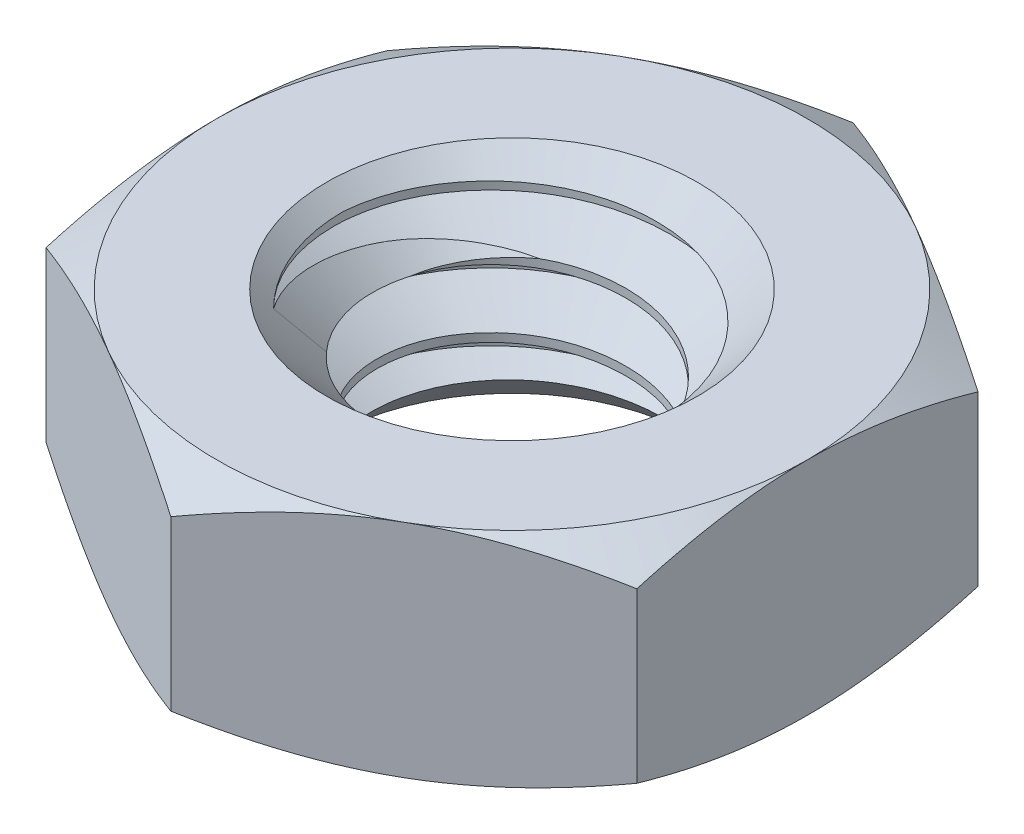
SolidWorks part; units mm, degrees
ref_plane "Front Plane" through (0, 0, 0) normal (0, 0, 1) x (1, 0, 0)
ref_plane "Top Plane" through (0, 0, 0) normal (0, 1, 0) x (1, 0, 0)
ref_plane "Right Plane" through (0, 0, 0) normal (1, 0, 0) x (0, 0, -1)
sketch "Sketch1" plane through (0, 0, 0) normal (0, 0, 1) x (1, 0, 0)
  line L0 (0, -2.0828) -> (0, 2.0828) construction
  line L1 (3.175, 2.0828) -> (-3.175, 2.0828) construction
  line L2 (-5.5626, -2.0828) -> (5.5626, -2.0828) construction
  line L3 (3.175, 2.0828) -> (3.175, 0.8128) construction
  point P4 (0, 0)
  point P8 (0, 2.0828)
  point P10 (0, -2.0828)
  dimension "Height" = 4.1656
  dimension "Width" = 11.1252
  dimension "Thread Dia" = 6.35
  dimension "Pitch" = 1.27
sketch "Sketch2" plane through (0, 0, 0) normal (0, 1, 0) x (1, 0, 0)
  line L1 (0, 6.4231) -> (-5.5626, 3.2116)
  line L2 (-5.5626, 3.2116) -> (-5.5626, -3.2116)
  line L3 (-5.5626, -3.2116) -> (0, -6.4231)
  line L4 (0, -6.4231) -> (5.5626, -3.2116)
  line L5 (5.5626, -3.2116) -> (5.5626, 3.2116)
  line L6 (5.5626, 3.2116) -> (0, 6.4231)
  circle A0 centre (0, 0) radius 5.5626 construction
  circle A1 centre (0, 0) radius 3.175
  point P11 (0, -3.175)
  point P14 (0, 0)
extrude "Boss-Extrude1" add sketch "Sketch2" along normal up to vertex (2.0828 mm away) and the other way up to vertex (2.0828 mm away) up to point (0, 2.0828, 0) other way up to point (0, -2.0828, 0)
sketch "Sketch3" plane through (0, 0, 0) normal (1, 0, 0) x (0, 0, -1)
  line L0 (-6.4231, 1.586) -> (-5.5626, 2.0828)
  line L1 (-6.4231, 2.0828) -> (-6.4231, -2.0828) construction
  line L2 (-6.4231, 2.0828) -> (-3.2116, 2.0828) construction
  line L3 (-6.4231, -1.586) -> (-5.5626, -2.0828)
  line L4 (-6.4231, -2.0828) -> (-3.2116, -2.0828) construction
  line L5 (-6.4231, 1.586) -> (-6.4231, 2.0828)
  line L6 (-6.4231, 2.0828) -> (-5.5626, 2.0828)
  line L7 (-6.4231, -1.586) -> (-6.4231, -2.0828)
  line L8 (-6.4231, -2.0828) -> (-5.5626, -2.0828)
  line L9 (-5.5626, 2.0828) -> (-5.5626, -2.0828) construction
  line L10 (-3.4925, 2.0828) -> (-3.175, 2.0828)
  line L11 (-3.2116, 2.0828) -> (3.2116, 2.0828) construction
  line L12 (-3.175, 2.0828) -> (-3.175, 1.7653)
  line L13 (-3.175, 1.7653) -> (-3.4925, 2.0828)
  line L14 (-3.4925, -2.0828) -> (-3.175, -2.0828)
  line L15 (-3.2116, -2.0828) -> (3.2116, -2.0828) construction
  line L16 (-3.175, -2.0828) -> (-3.175, -1.7653)
  line L17 (-3.4925, -2.0828) -> (-3.175, -1.7653)
  line L18 (-3.175, 1.7653) -> (-3.175, -1.7653) construction
  line L19 (3.175, 0) -> (-3.175, 0) construction
  line L22 (0, 2.0828) -> (0, -2.0828) construction
  point P15 (-5.5626, 0)
  point P24 (-3.175, 0)
  dimension "D1" = 30
  dimension "D2" = 3.4925
revolve "Cut-Revolve1" cut sketch "Sketch3" angle 360 about L22
sketch "Sketch4" plane through (0, 2.0828, 0) normal (0, 1, 0) x (1, 0, 0)
  circle A0 centre (0, 0) radius 3.175 construction
  circle A1 centre (0, 0) radius 3.175
extrude "Boss-Extrude2" add sketch "Sketch4" against normal up to surface (4.1656 mm away) separate body up to face at (0, -2.0828, 3.4925)
sketch "Sketch5" plane through (0, 2.0828, 0) normal (0, 1, 0) x (1, 0, 0)
  circle A0 centre (0, 0) radius 3.175 construction
  circle A1 centre (0, 0) radius 3.175
curve "Helix/Spiral1" pitch 1.27 height 5.4356 radius 3.175 centre (0, 2.0828, 0) axis (0, -1, 0) start towards (0, 0, 1)
sketch "Sketch6" plane through (0, 0, 0) normal (1, 0, 0) x (0, 0, -1)
  line L0 (-3.3125, 2.0034) -> (-2.2126, 2.6384) construction
  line L1 (-2.2126, 2.6384) -> (-3.3125, 3.2734) construction
  line L2 (-3.3125, 3.2734) -> (-3.3125, 2.0034) construction
  line L3 (-2.3501, 2.7178) -> (-2.3501, 2.559) construction
  line L4 (-3.175, 3.194) -> (-3.175, 2.0828) construction
  line L5 (-3.3125, 2.6384) -> (-3.175, 2.6384) construction
  line L6 (-2.3501, 2.6384) -> (-2.2126, 2.6384) construction
  line L7 (-3.2437, 2.6384) -> (-3.2437, 2.0431) construction
  line L8 (-3.2437, 2.0431) -> (-3.2437, 3.2337)
  line L9 (-3.2437, 3.2337) -> (-2.3501, 2.7178)
  line L10 (-2.3501, 2.7178) -> (-2.3501, 2.559)
  line L11 (-2.3501, 2.559) -> (-3.2437, 2.0431)
  dimension "D1" = 1.27
  dimension "D2" = 0.1588
sweep "Cut-Sweep1" cut profiles "Sketch6" path "Helix/Spiral1" align with end faces yes
sketch "Sketch7" plane through (0, 0, 0) normal (1, 0, 0) x (0, 0, -1)
  line L0 (-3.4925, 2.0828) -> (-1.905, 0.4953)
  line L2 (-3.4925, 2.0828) -> (0, 2.0828)
  line L3 (-3.4925, 2.0828) -> (-3.175, 2.0828) construction
  line L4 (-3.4925, -2.0828) -> (0, -2.0828)
  line L5 (-3.4925, -2.0828) -> (-3.175, -2.0828) construction
  line L6 (-3.4925, -2.0828) -> (-1.905, -0.4953)
  line L7 (-3.4925, -2.0828) -> (-3.175, -1.7653) construction
  line L8 (0, -2.0828) -> (0, 2.0828) construction
  line L9 (0, -2.0828) -> (0, 2.0828) construction
  line L12 (-1.905, 0.4953) -> (0, 0.4953)
  line L13 (0, 0.4953) -> (0, 2.0828)
  line L14 (-3.175, 1.7653) -> (-3.4925, 2.0828) construction
  line L15 (-1.905, -0.4953) -> (0, -0.4953)
  line L16 (0, -0.4953) -> (0, -2.0828)
  dimension "D1" = 1.905
revolve "Revolve1" add sketch "Sketch7" angle 360 about L9
sketch "Sketch8" plane through (0, 2.0828, 0) normal (0, 1, 0) x (1, 0, 0)
  circle A0 centre (0, 0) radius 3.4925 construction
  circle A1 centre (0, 0) radius 3.4925
extrude "Boss-Extrude3" add sketch "Sketch8" against normal up to surface (4.1656 mm away) up to face at (0, -2.0828, 3.4925)
combine bodies "Combine1" operation type subtract main body 109 bodies to subtract 108
equation "\"D2@Sketch3\"=\"Thread Dia@Sketch1\"*.55"
equation "\"D4@Helix/Spiral1\"=\"Pitch@Sketch1\""
equation "\"D3@Helix/Spiral1\"=\"Height@Sketch1\"+\"Pitch@Sketch1\""
equation "\"D1@Sketch6\"=\"Pitch@Sketch1\""
equation "\"D2@Sketch6\"=\"Pitch@Sketch1\"/8"
equation "\"D1@Sketch7\"=\"Thread Dia@Sketch1\"*.3"
